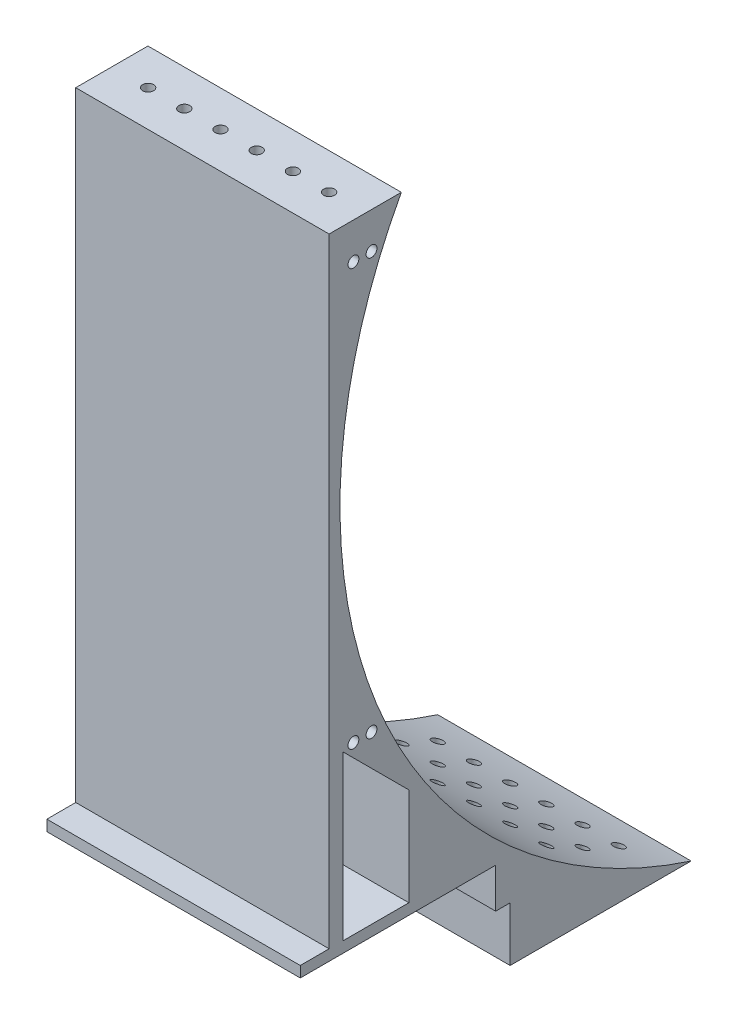
SolidWorks part; units mm, degrees
ref_plane "Front Plane" through (0, 0, 0) normal (0, 0, 1) x (1, 0, 0)
ref_plane "Top Plane" through (0, 0, 0) normal (0, 1, 0) x (1, 0, 0)
ref_plane "Right Plane" through (0, 0, 0) normal (1, 0, 0) x (0, 0, -1)
sketch "Sketch1" plane through (0, 0, 0) normal (1, 0, 0) x (0, 0, -1)
  line L0 (0, 200) -> (0, 0)
  line L1 (0, 0) -> (100, 0)
  line L2 (0, 200) -> (19.9466, 200)
  arc A0 (19.9466, 200) -> (100, 0) centre (143, 133.2329) ccw
  dimension "D1" = 140
  dimension "D4" = 143
  dimension "D2" = 200
extrude "Boss-Extrude1" add sketch "Sketch1" along normal blind 70
ref_plane "Plane1" through (0, 0, -100) normal (0, 0, 1) x (1, 0, 0)
sketch "Sketch5" plane through (70, 0, 0) normal (1, 0, 0) x (0, 0, -1)
  line L0 (22.0273, 26) -> (22.0273, 56)
  line L1 (0, 0) -> (50, 0)
  line L3 (22.0273, 26) -> (46, 26)
  line L4 (50, 0) -> (50, 15)
  line L5 (22.0273, 56) -> (3.8589, 74.1684)
  line L7 (0, 26) -> (0, 0)
  line L8 (3.8589, 74.1684) -> (3.8589, 26)
  line L11 (50, 15) -> (46, 15)
  line L12 (46, 26) -> (46, 15)
  line L13 (3.8589, 26) -> (0, 26)
  dimension "D1" = 135
  dimension "D2" = 50
  dimension "D3" = 15
  dimension "D4" = 30
  dimension "D5" = 4
  dimension "D6" = 11
extrude "Cut-Extrude2" cut sketch "Sketch5" against normal through all
sketch "Sketch6" plane through (0, 0, -22.0273) normal (0, 0, 1) x (1, 0, 0)
  line L0 (70, 26) -> (70, 56) construction
  line L1 (0, 26) -> (70, 26)
  line L2 (0, 26) -> (0, 29)
  line L3 (0, 29) -> (70, 29)
  line L4 (70, 26) -> (70, 29)
  dimension "D1" = 3
extrude "Boss-Extrude2" add sketch "Sketch6" along normal blind 30
sketch "Sketch7" plane through (0, 200, 0) normal (0, 1, 0) x (1, 0, 0)
  line L1 (0, 19.9466) -> (0, 0) construction
  line L2 (70, 0) -> (0, 0) construction
  circle A0 centre (10, 10) radius 1.5
  circle A1 centre (20, 10) radius 1.5
  circle A2 centre (30, 10) radius 1.5
  circle A3 centre (40, 10) radius 1.5
  circle A4 centre (50, 10) radius 1.5
  circle A5 centre (60, 10) radius 1.5
  dimension "D2" = 3
  dimension "D3" = 10
  dimension "D1" = 10
  dimension "D4" = 6
extrude "Cut-Extrude3" cut sketch "Sketch7" against normal blind 20
sketch "Sketch8" plane through (0, 0, 0) normal (0, -1, 0) x (1, 0, 0)
  line L0 (70, -100) -> (0, -100) construction
  line L1 (0, -50) -> (0, -100) construction
  circle A0 centre (10, -90) radius 1.5
  circle A1 centre (20, -90) radius 1.5
  circle A2 centre (30, -90) radius 1.5
  circle A3 centre (40, -90) radius 1.5
  circle A4 centre (50, -90) radius 1.5
  circle A5 centre (60, -90) radius 1.5
  circle A6 centre (20, -80) radius 1.5
  circle A7 centre (30, -80) radius 1.5
  circle A8 centre (40, -80) radius 1.5
  circle A9 centre (50, -80) radius 1.5
  circle A10 centre (60, -80) radius 1.5
  circle A11 centre (20, -70) radius 1.5
  circle A12 centre (30, -70) radius 1.5
  circle A13 centre (40, -70) radius 1.5
  circle A14 centre (50, -70) radius 1.5
  circle A15 centre (60, -70) radius 1.5
  circle A16 centre (20, -60) radius 1.5
  circle A17 centre (30, -60) radius 1.5
  circle A18 centre (40, -60) radius 1.5
  circle A19 centre (50, -60) radius 1.5
  circle A20 centre (60, -60) radius 1.5
  circle A21 centre (10, -80) radius 1.5
  circle A22 centre (10, -70) radius 1.5
  circle A23 centre (10, -60) radius 1.5
  dimension "D1" = 3
  dimension "D2" = 10
  dimension "D3" = 10
  dimension "D4" = 6
  dimension "D5" = 4
extrude "Cut-Extrude4" cut sketch "Sketch8" against normal blind 15
sketch "Sketch9" plane through (0, 26, 0) normal (0, -1, 0) x (1, 0, 0)
  line L0 (35, 7.9727) -> (35, -46) construction
  line L1 (0, 7.9727) -> (70, 7.9727) construction
  line L2 (0, -46) -> (70, -46) construction
  line L3 (0, -46) -> (70, -46) construction
  circle A0 centre (20, -6) radius 1.5
  circle A1 centre (20, -31) radius 1.5
  circle A2 centre (50, -31) radius 1.5
  circle A3 centre (50, -6) radius 1.5
  dimension "D1" = 3
  dimension "D2" = 3
  dimension "D3" = 25
  dimension "D4" = 15
  dimension "D5" = 15
extrude "Cut-Extrude5" cut sketch "Sketch9" against normal blind 20
sketch "Sketch10" plane through (70, 0, 0) normal (1, 0, 0) x (0, 0, -1)
  line L0 (46, 26) -> (-7.9727, 26) construction
  line L1 (0, 200) -> (0, 29) construction
  circle A0 centre (6.71, 75) radius 1.5
  circle A2 centre (11.71, 75) radius 1.5
  circle A3 centre (6.71, 190) radius 1.5
  circle A4 centre (11.71, 190) radius 1.5
  dimension "D2" = 3
  dimension "D3" = 6.71
  dimension "D6" = 5
  dimension "D7" = 115
  dimension "D1" = 49
  dimension "D4" = 2
  dimension "D5" = 2
extrude "Cut-Extrude6" cut sketch "Sketch10" against normal through all
